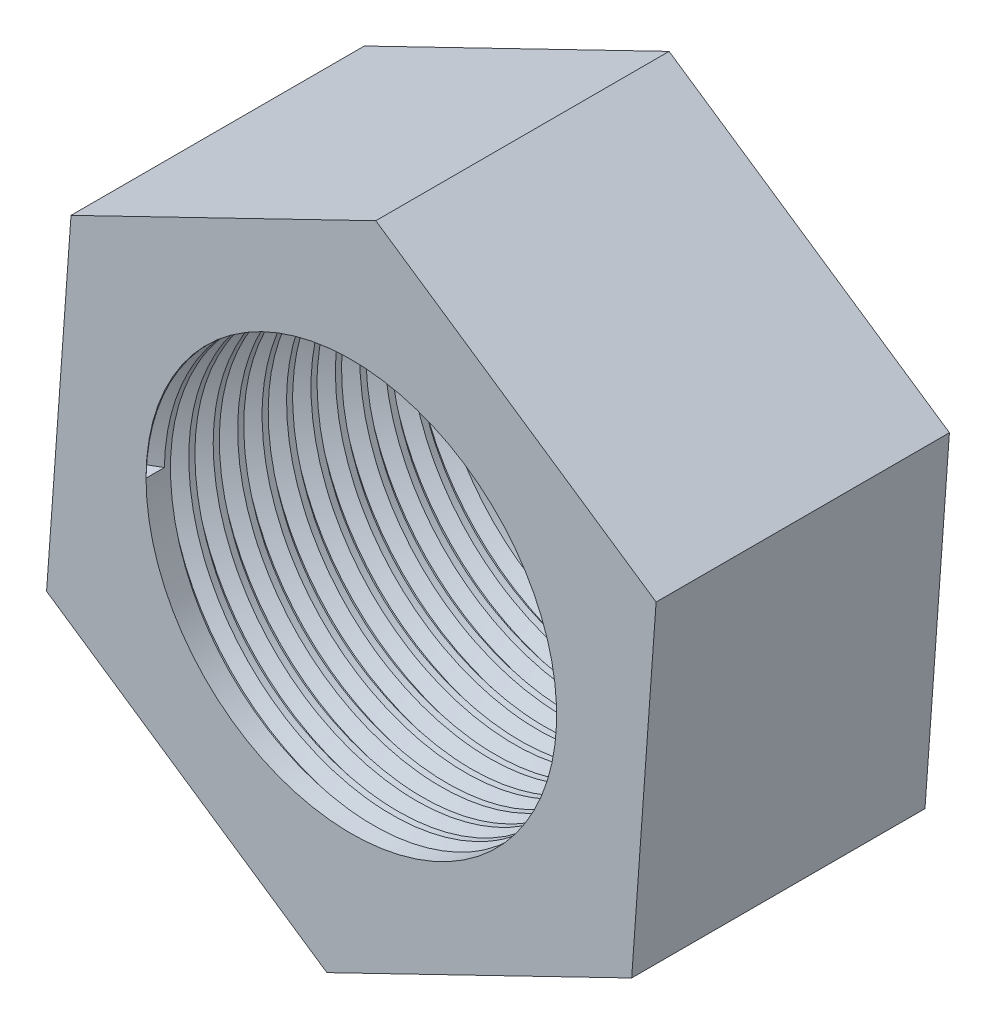
SolidWorks part; units mm, degrees
ref_plane "Front Plane" through (0, 0, 0) normal (0, 0, 1) x (1, 0, 0)
ref_plane "Top Plane" through (0, 0, 0) normal (0, 1, 0) x (1, 0, 0)
ref_plane "Right Plane" through (0, 0, 0) normal (1, 0, 0) x (0, 0, -1)
sketch "Sketch1" plane through (0, 0, 0) normal (0, 0, 1) x (1, 0, 0)
  line L1 (-2.8672, 1.9441) -> (-3.1172, -1.511)
  line L2 (-3.1172, -1.511) -> (-0.25, -3.4551)
  line L3 (-0.25, -3.4551) -> (2.8672, -1.9441)
  line L4 (2.8672, -1.9441) -> (3.1172, 1.511)
  line L5 (3.1172, 1.511) -> (0.25, 3.4551)
  line L6 (0.25, 3.4551) -> (-2.8672, 1.9441)
  circle A0 centre (0, 0) radius 3 construction
extrude "Boss-Extrude1" add sketch "Sketch1" along normal blind 3
sketch "Sketch2" plane through (0, 0, 3) normal (0, 0, 1) x (1, 0, 0)
  circle A0 centre (0, 0) radius 2.1
extrude "Cut-Extrude1" cut sketch "Sketch2" against normal through all
thread "Thread1" pitch 0.25 method cut profile "Thread Profile1" start angle 0, offset 0, length 0, pitch 0.25, diameter 4.2
ref_plane "Plane1" through (-2.1, 0, 3) normal (0, -1, 0) x (-1, 0, 0)
sketch "Thread Profile1" plane through (-2.1, 0, 3) normal (0, -1, 0) x (-1, 0, 0)
  line L0 (0, 0) -> (0, 0.25) construction
  line L1 (0, 0) -> (0.1353, 0.0781)
  line L2 (0.1353, 0.0781) -> (0.1353, 0.1094)
  line L3 (0.1353, 0.1094) -> (0, 0.1875)
  line L4 (0.1353, 0.0937) -> (0, 0.0937) construction
  line L11 (0, 0) -> (0, 0.1875)
  point P2 (0, 0)
  dimension "Pitch" = 0.25
  dimension "Profile_Angle" = 60
  dimension "Profile_Land" = 0.0312
  dimension "Profile_Height" = 0.1353
